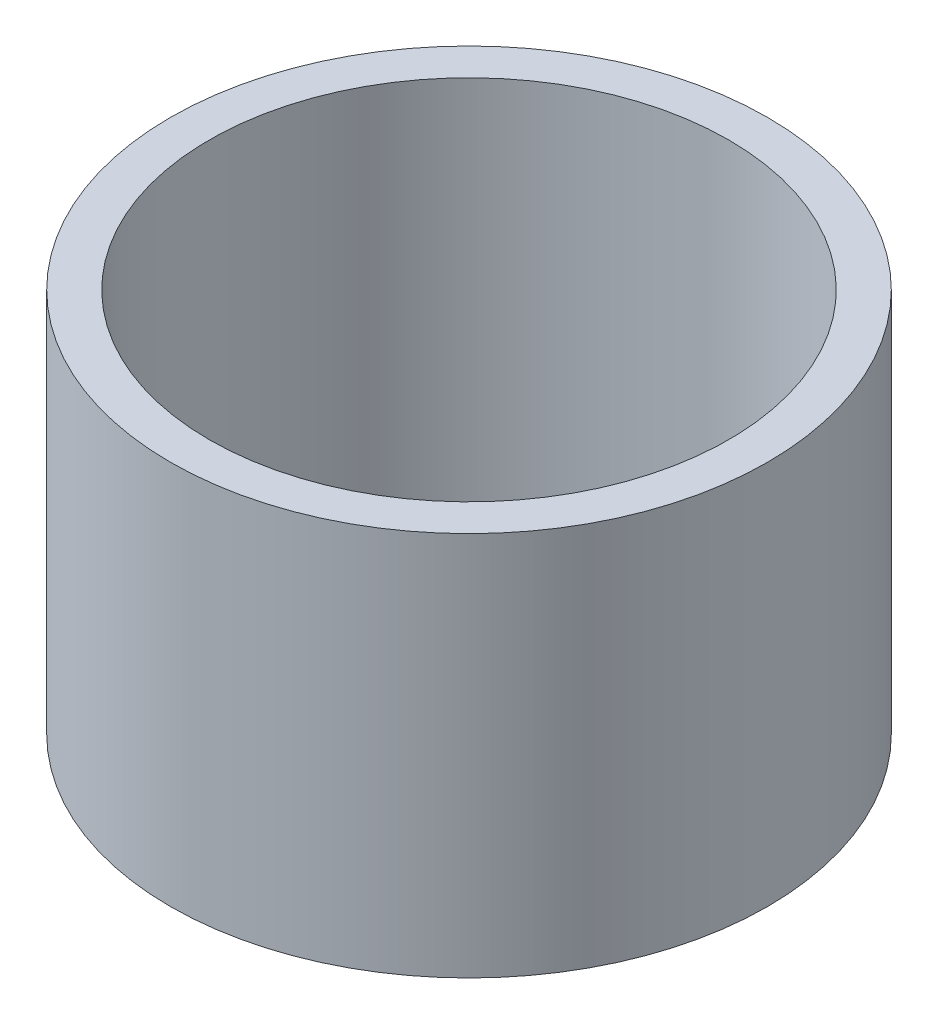
SolidWorks part; units mm, degrees
ref_plane "Front Plane" through (0, 0, 0) normal (0, 0, 1) x (1, 0, 0)
ref_plane "Top Plane" through (0, 0, 0) normal (0, 1, 0) x (1, 0, 0)
ref_plane "Right Plane" through (0, 0, 0) normal (1, 0, 0) x (0, 0, -1)
sketch "Sketch1" plane through (0, 0, 0) normal (0, 1, 0) x (1, 0, 0)
  circle A0 centre (0, 0) radius 37.946
  dimension "D1" = 75.892
extrude "Boss-Extrude1" add sketch "Sketch1" along normal blind 48.9
sketch "Sketch2" plane through (0, 48.9, 0) normal (0, 1, 0) x (1, 0, 0)
  circle A0 centre (0, 0) radius 33
  dimension "D1" = 66
extrude "Cut-Extrude1" cut sketch "Sketch2" against normal blind 46.9
sketch "Sketch3" plane through (0, 0, 0) normal (0, -1, 0) x (1, 0, 0)
  circle A0 centre (0, 0) radius 3.925
  dimension "D1" = 7.85
extrude "Boss-Extrude2" add sketch "Sketch3" along normal blind 10
